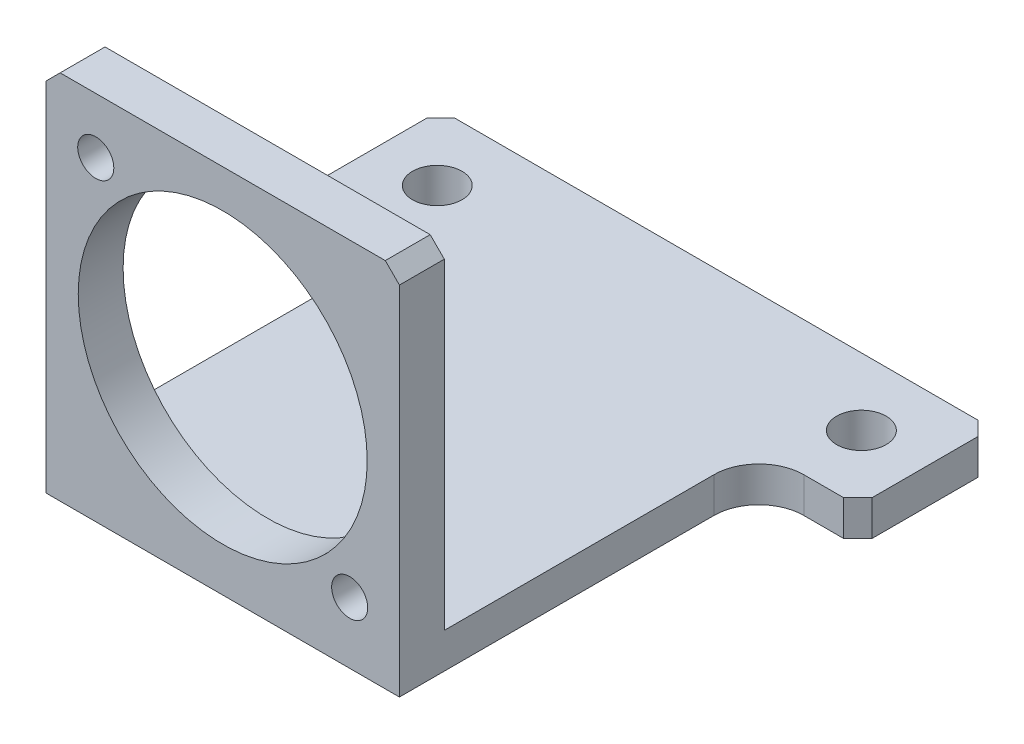
SolidWorks part; units mm, degrees
material "PVC Rigid"
ref_plane "Front Plane" through (0, 0, 0) normal (0, 0, 1) x (1, 0, 0)
ref_plane "Top Plane" through (0, 0, 0) normal (0, 1, 0) x (1, 0, 0)
ref_plane "Right Plane" through (0, 0, 0) normal (1, 0, 0) x (0, 0, -1)
other "PLA"
sketch "Sketch1" plane through (0, 0, 0) normal (0, 0, 1) x (1, 0, 0)
  line L0 (0, 26.24) -> (0, 0.415) construction
  line L1 (-25, -26.24) -> (25, -26.24)
  line L2 (-25, -26.24) -> (-25, 26.24)
  line L3 (-25, 26.24) -> (25, 26.24)
  line L4 (25, -26.24) -> (25, 26.24)
  line L5 (-25, -26.24) -> (25, 26.24) construction
  line L6 (-25, 26.24) -> (25, -26.24) construction
  line L7 (0, 0.415) -> (-25, 0.415) construction
  circle A1 centre (0, 0.415) radius 20.44
  point P0 (0, 0)
  dimension "D3" = 40.88
  dimension "D4" = 25.825
  dimension "D1" = 50
  dimension "D2" = 52.48
extrude "Boss-Extrude1" add sketch "Sketch1" along normal blind 6.35
sketch "Sketch4" plane through (0, -26.24, 0) normal (0, -1, 0) x (1, 0, 0)
  line L0 (25, 0) -> (25, -63.5)
  line L1 (25, -63.5) -> (-25, -63.5)
  line L2 (-25, -63.5) -> (-25, 0)
  line L3 (-25, -63.5) -> (-39, -63.5)
  line L4 (-25, 0) -> (25, 0)
  line L5 (25, 0) -> (25, 6.35)
  line L6 (25, 6.35) -> (-25, 6.35)
  line L7 (-25, 6.35) -> (-25, 0)
  line L8 (-25, 0) -> (25, 0)
  line L9 (25, 0) -> (25, 6.35)
  line L10 (25, 6.35) -> (-25, 6.35)
  line L11 (-25, 6.35) -> (-25, 0)
  line L12 (-39, -63.5) -> (-39, -44.5)
  line L13 (-39, -44.5) -> (-25, -44.5)
  line L14 (25, -44.5) -> (39, -44.5)
  line L15 (39, -44.5) -> (39, -63.5)
  line L16 (39, -63.5) -> (25, -63.5)
  line L17 (-30, -54) -> (30, -54) construction
  line L18 (0, 0) -> (0, -54) construction
  circle A0 centre (-30, -54) radius 3.5
  circle A1 centre (30, -54) radius 3.5
  line M6 (-25, 0) -> (25, 0)
  dimension "D5" = 7
  dimension "D6" = 54
  dimension "D4" = 6
  dimension "D2" = 6
  dimension "D3" = 14
  dimension "D8" = 60
  dimension "D1" = 0
extrude "Boss-Extrude4" add sketch "Sketch4" against normal blind 5 contours L2 L1 L0 M6 | L13 L12 L3 L2 A0 | L16 L15 L14 L0 A1 | L17 L2 L1 L0 region at (0, -26.24, -31.75) region at (32, -26.24, -44.736) region at (-25.236, -26.24, -54)
sketch "Sketch6" plane through (0, 0, 6.35) normal (0, 0, 1) x (1, 0, 0)
  line L0 (0, 20.855) -> (0, 0.415) construction
  line L1 (0, 0.415) -> (-17.9605, 18.3755) construction
  line L2 (0, 0.415) -> (17.9605, -17.5455) construction
  line L4 (25, -26.24) -> (25, 26.24)
  line L5 (25, 26.24) -> (-25, 26.24)
  line L6 (-25, 26.24) -> (-25, -26.24)
  line L7 (-25, -26.24) -> (25, -26.24)
  line L8 (25, -26.24) -> (25, 26.24)
  line L9 (25, 26.24) -> (-25, 26.24)
  line L10 (-25, 26.24) -> (-25, -26.24)
  line L11 (-25, -26.24) -> (25, -26.24)
  circle A0 centre (0, 0.415) radius 25.4
  circle A1 centre (0, 0.415) radius 20.44 construction
  circle A2 centre (0, 0.415) radius 20.44 construction
  circle A13 centre (-17.9605, 18.3755) radius 1.8397 construction
  circle A14 centre (17.9605, -17.5455) radius 2.6097 construction
  dimension "D2" = 50.8
  dimension "D3" = 45
  dimension "D1" = 0
hole_wizard "#10 Clearance Hole1" positions "Sketch7" profile "Sketch8" hole size "#10" standard "ANSI Inch" end condition up to next
sketch "Sketch7" plane through (0, 0, 6.35) normal (0, 0, 1) x (1, 0, 0)
  line L8 (25, -26.24) -> (25, 26.24)
  line L9 (25, 26.24) -> (-25, 26.24)
  line L10 (-25, 26.24) -> (-25, -26.24)
  line L11 (-25, -26.24) -> (25, -26.24)
  line L12 (25, -26.24) -> (25, 26.24)
  line L13 (25, 26.24) -> (-25, 26.24)
  line L14 (-25, 26.24) -> (-25, -26.24)
  line L15 (-25, -26.24) -> (25, -26.24)
  point P17 (-17.9605, 18.3755)
  point P20 (17.9605, -17.5455)
  dimension "D1" = 0
sketch "Sketch8" plane through (17.9605, -17.5455, 6.35) normal (1, 0, 0) x (0, -1, 0)
  line L0 (0, 0) -> (0, 6.35)
  line L1 (0, 6.35) -> (2.5527, 6.35)
  line L2 (2.5527, 6.35) -> (2.5527, 0)
  line L5 (2.5527, 0) -> (0, 0)
  line L11 (0, -6.35) -> (0, 107.95) construction
  dimension "Thru Hole Dia." = 5.1054
  dimension "Thru Hole Depth" = 6.35
fillet "Fillet1" radius 6.35 2 edges at (25, -23.74, -44.5) (-25, -23.74, -44.5)
chamfer "Chamfer1" distance 2 angle 45 4 edges at (-39, -23.74, -63.5) (-39, -23.74, -44.5) (39, -23.74, -63.5) (39, -23.74, -44.5)
chamfer "Chamfer2" distance 2 angle 45 2 edges at (25, 26.24, 3.175) (-25, 26.24, 3.175)
